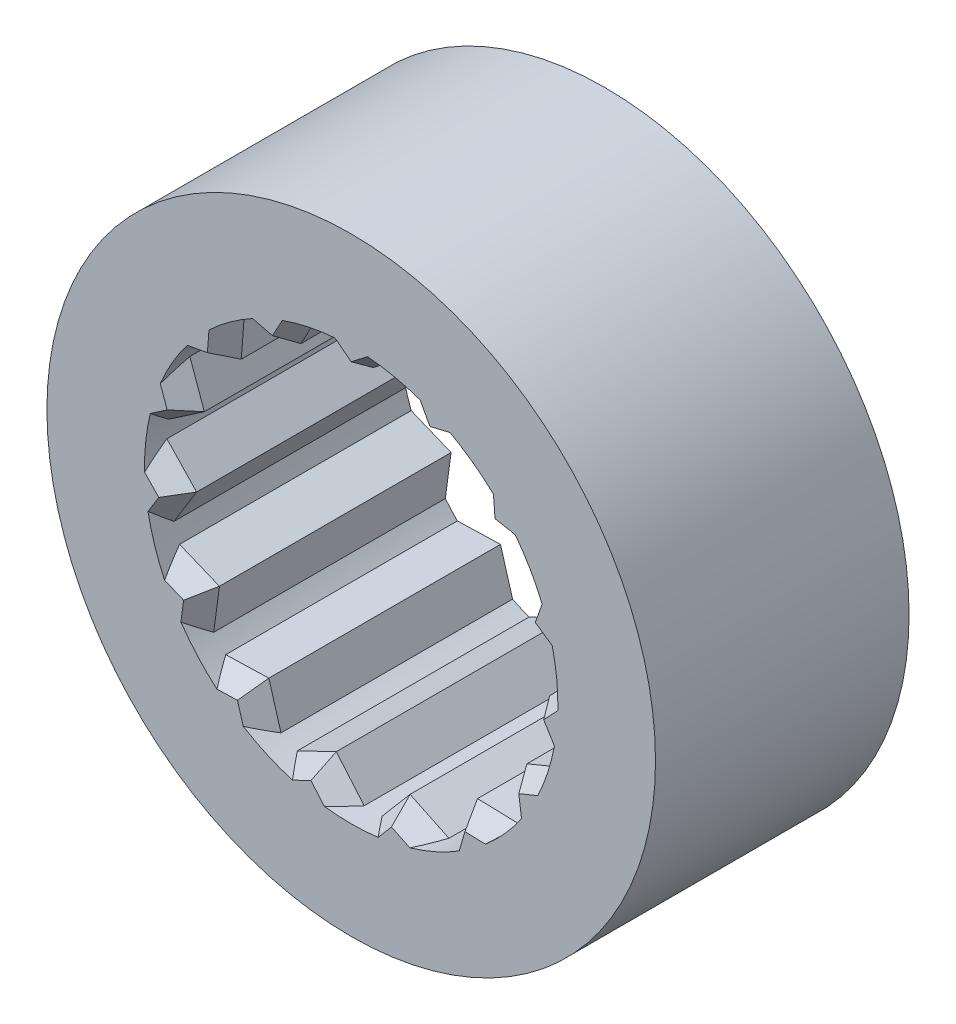
SolidWorks part; units mm, degrees
note: The reader was unsure of these and kept them because the rebuilt part matched: shared geometry of "Sketch1<4>".
ref_plane "Front Plane" through (0, 0, 0) normal (0, 0, 1) x (1, 0, 0)
ref_plane "Top Plane" through (0, 0, 0) normal (0, 1, 0) x (1, 0, 0)
ref_plane "Right Plane" through (0, 0, 0) normal (1, 0, 0) x (0, 0, -1)
sketch "Sketch1" plane through (0, 0, 0) normal (0, 0, 1) x (1, 0, 0)
  line L0 (0, 3.5) -> (-0.6731, 4.019)
  line L1 (0, 3.5) -> (0.6731, 4.019)
  circle A0 centre (0, 0) radius 6
  circle A1 centre (0, 0) radius 4.075
  circle A2 centre (0, 0) radius 3.5 construction
  point P7 (0, 0)
  point P9 (0.8152, 3.8139)
  dimension "D1" = 8.15
  dimension "D2" = 7
  dimension "D3" = 12
  dimension "D4" = 0.85
extrude "ring" add sketch "Sketch1" along normal blind 5 contours A0 A1
extrude "single teeth" add sketch "Sketch1<4>" along normal blind 5 contours L1 A1 L0
sketch "Sketch1<4>" plane through (0, 0, 0) normal (0, 0, 1) x (1, 0, 0) same geometry as "Sketch1"
chamfer "teethChampfer" distance 0.25 angle 60 2 edges at (-0.3366, 3.7595, 5) (0.3366, 3.7595, 5)
pattern_circular "15th teeths" count 15 over 360 about axis through (0, 0, 0) along (0, 0, 1) of "single teeth", "teethChampfer"
